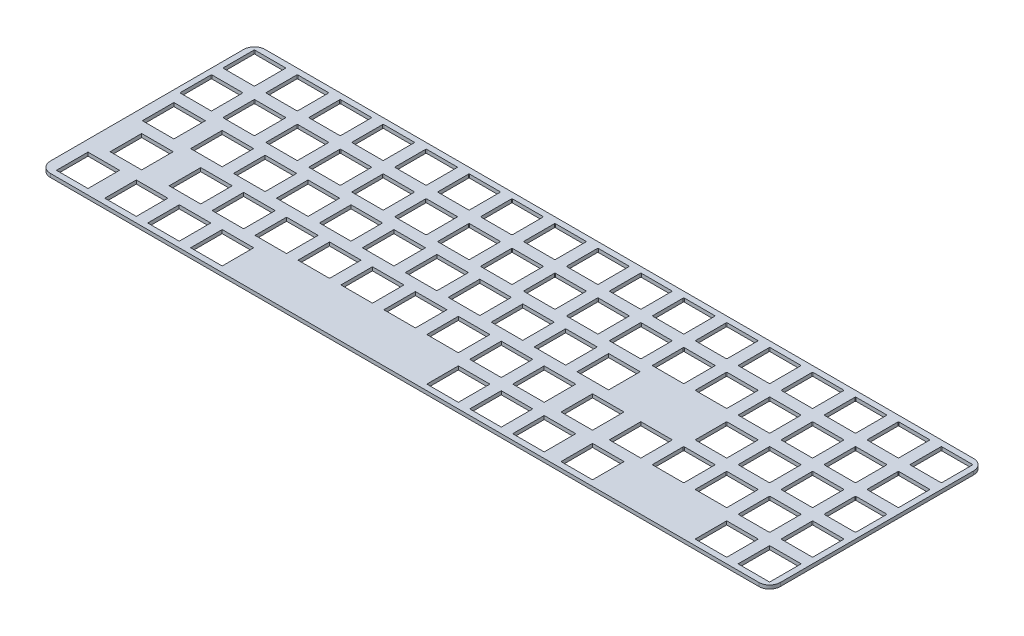
SolidWorks part; units mm, degrees
ref_plane "Front" through (0, 0, 0) normal (0, 0, 1) x (1, 0, 0)
ref_plane "Top" through (0, 0, 0) normal (0, 1, 0) x (1, 0, 0)
ref_plane "Right" through (0, 0, 0) normal (1, 0, 0) x (0, 0, -1)
sketch "Sketch1" plane through (0, 0, 0) normal (0, 1, 0) x (1, 0, 0)
  line L0 (-161.925, 28.575) -> (161.925, 28.575)
  line L1 (161.925, -47.625) -> (-161.925, -47.625)
  line L2 (161.925, -47.625) -> (161.925, 47.625)
  line L3 (161.925, 47.625) -> (-161.925, 47.625)
  line L4 (-161.925, -47.625) -> (-161.925, 47.625)
  line L5 (-123.825, 47.625) -> (-123.825, 28.575)
  line L6 (-104.775, 47.625) -> (-104.775, 28.575)
  line L7 (-142.875, 47.625) -> (-142.875, 28.575)
  line L8 (-85.725, 47.625) -> (-85.725, 28.575)
  line L9 (-66.675, 47.625) -> (-66.675, 28.575)
  line L10 (-47.625, 47.625) -> (-47.625, 28.575)
  line L11 (-28.575, 47.625) -> (-28.575, 28.575)
  line L12 (-9.525, 47.625) -> (-9.525, 28.575)
  line L13 (9.525, 47.625) -> (9.525, 28.575)
  line L14 (28.575, 47.625) -> (28.575, 28.575)
  line L15 (47.625, 47.625) -> (47.625, 28.575)
  line L16 (66.675, 47.625) -> (66.675, 28.575)
  line L17 (85.725, 47.625) -> (85.725, 28.575)
  line L18 (104.775, 47.625) -> (104.775, 28.575)
  line L19 (123.825, 47.625) -> (123.825, 28.575)
  line L20 (142.875, 47.625) -> (142.875, 28.575)
  line L21 (-142.875, 47.625) -> (-123.825, 47.625) construction
  line L22 (-161.925, 9.525) -> (161.925, 9.525)
  line L23 (-142.875, 28.575) -> (-142.875, 9.525)
  line L24 (-123.825, 28.575) -> (-123.825, 9.525)
  line L25 (-104.775, 28.575) -> (-104.775, 9.525)
  line L26 (-85.725, 28.575) -> (-85.725, 9.525)
  line L27 (-66.675, 28.575) -> (-66.675, 9.525)
  line L28 (-47.625, 28.575) -> (-47.625, 9.525)
  line L29 (-28.575, 28.575) -> (-28.575, 9.525)
  line L30 (-9.525, 28.575) -> (-9.525, 9.525)
  line L31 (9.525, 28.575) -> (9.525, 9.525)
  line L32 (28.575, 28.575) -> (28.575, 9.525)
  line L33 (47.625, 28.575) -> (47.625, 9.525)
  line L34 (66.675, 28.575) -> (66.675, 9.525)
  line L35 (85.725, 28.575) -> (85.725, 9.525)
  line L36 (104.775, 28.575) -> (104.775, 9.525)
  line L37 (123.825, 28.575) -> (123.825, 9.525)
  line L38 (142.875, 28.575) -> (142.875, 9.525)
  line L39 (-142.875, 28.575) -> (-123.825, 28.575) construction
  line L40 (-161.925, -9.525) -> (161.925, -9.525)
  line L41 (-161.925, -28.575) -> (161.925, -28.575)
  line L42 (-138.1125, 9.525) -> (-138.1125, -9.525)
  line L43 (-128.5875, -9.525) -> (-128.5875, -28.575)
  line L44 (-138.1125, -28.575) -> (-138.1125, -47.625)
  line L45 (-119.0625, 9.525) -> (-119.0625, -9.525)
  line L46 (-100.0125, 9.525) -> (-100.0125, -9.525)
  line L47 (-80.9625, 9.525) -> (-80.9625, -9.525)
  line L48 (-61.9125, 9.525) -> (-61.9125, -9.525)
  line L49 (-42.8625, 9.525) -> (-42.8625, -9.525)
  line L50 (-23.8125, 9.525) -> (-23.8125, -9.525)
  line L51 (-4.7625, 9.525) -> (-4.7625, -9.525)
  line L52 (14.2875, 9.525) -> (14.2875, -9.525)
  line L53 (33.3375, 9.525) -> (33.3375, -9.525)
  line L54 (-138.1125, 9.525) -> (-119.0625, 9.525) construction
  line L55 (52.3875, 9.525) -> (52.3875, -9.525)
  line L56 (85.725, 9.525) -> (85.725, -9.525)
  line L57 (-109.5375, -9.525) -> (-109.5375, -28.575)
  line L58 (-90.4875, -9.525) -> (-90.4875, -28.575)
  line L59 (-71.4375, -9.525) -> (-71.4375, -28.575)
  line L60 (-52.3875, -9.525) -> (-52.3875, -28.575)
  line L61 (-33.3375, -9.525) -> (-33.3375, -28.575)
  line L62 (-14.2875, -9.525) -> (-14.2875, -28.575)
  line L63 (4.7625, -9.525) -> (4.7625, -28.575)
  line L64 (23.8125, -9.525) -> (23.8125, -28.575)
  line L65 (42.8625, -9.525) -> (42.8625, -28.575)
  line L66 (-128.5875, -9.525) -> (-109.5375, -9.525) construction
  line L67 (66.675, -9.525) -> (66.675, -28.575)
  line L68 (85.725, -9.525) -> (85.725, -28.575)
  line L69 (-119.0625, -28.575) -> (-119.0625, -47.625)
  line L70 (-100.0125, -28.575) -> (-100.0125, -47.625)
  line L71 (-80.9625, -28.575) -> (-80.9625, -47.625)
  line L72 (-138.1125, -28.575) -> (-119.0625, -28.575) construction
  line L73 (-47.625, -28.575) -> (-47.625, -47.625)
  line L74 (4.7625, -28.575) -> (4.7625, -47.625)
  line L75 (23.8125, -28.575) -> (23.8125, -47.625)
  line L76 (42.8625, -28.575) -> (42.8625, -47.625)
  line L77 (61.9125, -28.575) -> (61.9125, -47.625)
  line L78 (85.725, -28.575) -> (85.725, -47.625)
  line L79 (104.775, 9.525) -> (104.775, -9.525)
  line L80 (104.775, -9.525) -> (104.775, -28.575)
  line L81 (123.825, 9.525) -> (123.825, -9.525)
  line L82 (123.825, -9.525) -> (123.825, -28.575)
  line L83 (123.825, -28.575) -> (123.825, -47.625)
  line L84 (142.875, 9.525) -> (142.875, -9.525)
  line L85 (142.875, -9.525) -> (142.875, -28.575)
  line L86 (142.875, -28.575) -> (142.875, -47.625)
  line L87 (-161.925, 47.625) -> (-142.875, 28.575) construction
  line L88 (-142.875, 28.575) -> (-161.925, 9.525) construction
  line L89 (-161.925, 9.525) -> (-138.1125, -9.525) construction
  line L90 (-138.1125, -9.525) -> (-119.0625, 9.525) construction
  line L91 (-119.0625, 9.525) -> (-100.0125, -9.525) construction
  line L92 (-100.0125, -9.525) -> (-80.9625, 9.525) construction
  line L93 (-80.9625, 9.525) -> (-61.9125, -9.525) construction
  line L94 (-61.9125, -9.525) -> (-42.8625, 9.525) construction
  line L95 (-42.8625, 9.525) -> (-23.8125, -9.525) construction
  line L96 (-23.8125, -9.525) -> (-4.7625, 9.525) construction
  line L97 (-4.7625, 9.525) -> (14.2875, -9.525) construction
  line L98 (14.2875, -9.525) -> (33.3375, 9.525) construction
  line L99 (33.3375, 9.525) -> (52.3875, -9.525) construction
  line L100 (52.3875, -9.525) -> (85.725, 9.525) construction
  line L101 (85.725, 9.525) -> (104.775, -9.525) construction
  line L102 (104.775, -9.525) -> (85.725, -28.575) construction
  line L103 (85.725, -47.625) -> (123.825, -28.575) construction
  line L104 (85.725, -28.575) -> (123.825, -47.625) construction
  line L105 (123.825, -28.575) -> (104.775, -9.525) construction
  line L106 (104.775, -9.525) -> (123.825, 9.525) construction
  line L107 (123.825, 9.525) -> (104.775, 28.575) construction
  line L108 (104.775, 28.575) -> (123.825, 47.625) construction
  line L109 (123.825, 47.625) -> (142.875, 28.575) construction
  line L110 (142.875, 28.575) -> (123.825, 9.525) construction
  line L111 (123.825, 9.525) -> (142.875, -9.525) construction
  line L112 (142.875, -9.525) -> (123.825, -28.575) construction
  line L113 (123.825, -28.575) -> (142.875, -47.625) construction
  line L114 (142.875, -47.625) -> (161.925, -28.575) construction
  line L115 (161.925, -28.575) -> (142.875, -9.525) construction
  line L116 (142.875, -9.525) -> (161.925, 9.525) construction
  line L117 (161.925, 9.525) -> (142.875, 28.575) construction
  line L118 (142.875, 28.575) -> (161.925, 47.625) construction
  line L119 (161.925, -47.625) -> (142.875, -28.575) construction
  line L120 (142.875, -28.575) -> (123.825, -47.625) construction
  line L121 (85.725, -47.625) -> (61.9125, -28.575) construction
  line L122 (61.9125, -28.575) -> (42.8625, -47.625) construction
  line L123 (42.8625, -47.625) -> (23.8125, -28.575) construction
  line L124 (23.8125, -28.575) -> (42.8625, -9.525) construction
  line L125 (42.8625, -9.525) -> (66.675, -28.575) construction
  line L126 (66.675, -28.575) -> (85.725, -9.525) construction
  line L127 (85.725, -9.525) -> (104.775, -28.575) construction
  line L128 (104.775, -28.575) -> (123.825, -9.525) construction
  line L129 (123.825, -9.525) -> (142.875, -28.575) construction
  line L130 (142.875, -28.575) -> (161.925, -9.525) construction
  line L131 (161.925, -9.525) -> (142.875, 9.525) construction
  line L132 (142.875, 9.525) -> (123.825, -9.525) construction
  line L133 (123.825, -9.525) -> (104.775, 9.525) construction
  line L134 (104.775, 9.525) -> (85.725, -9.525) construction
  line L135 (85.725, -9.525) -> (52.3875, 9.525) construction
  line L136 (52.3875, 9.525) -> (33.3375, -9.525) construction
  line L137 (33.3375, -9.525) -> (14.2875, 9.525) construction
  line L138 (14.2875, 9.525) -> (-4.7625, -9.525) construction
  line L139 (-4.7625, -9.525) -> (-23.8125, 9.525) construction
  line L140 (-23.8125, 9.525) -> (-42.8625, -9.525) construction
  line L141 (-42.8625, -9.525) -> (-61.9125, 9.525) construction
  line L142 (-61.9125, 9.525) -> (-80.9625, -9.525) construction
  line L143 (-80.9625, -9.525) -> (-100.0125, 9.525) construction
  line L144 (-100.0125, 9.525) -> (-119.0625, -9.525) construction
  line L145 (-119.0625, -9.525) -> (-138.1125, 9.525) construction
  line L146 (-138.1125, 9.525) -> (-161.925, -9.525) construction
  line L147 (-161.925, -9.525) -> (-128.5875, -28.575) construction
  line L148 (-128.5875, -28.575) -> (-109.5375, -9.525) construction
  line L149 (-109.5375, -9.525) -> (-90.4875, -28.575) construction
  line L150 (-90.4875, -28.575) -> (-71.4375, -9.525) construction
  line L151 (-71.4375, -9.525) -> (-52.3875, -28.575) construction
  line L152 (-52.3875, -28.575) -> (-33.3375, -9.525) construction
  line L153 (-33.3375, -9.525) -> (-14.2875, -28.575) construction
  line L154 (-14.2875, -28.575) -> (4.7625, -9.525) construction
  line L155 (4.7625, -9.525) -> (23.8125, -28.575) construction
  line L156 (23.8125, -28.575) -> (4.7625, -47.625) construction
  line L157 (4.7625, -47.625) -> (-47.625, -28.575) construction
  line L158 (-47.625, -28.575) -> (-80.9625, -47.625) construction
  line L159 (-80.9625, -47.625) -> (-100.0125, -28.575) construction
  line L160 (-100.0125, -28.575) -> (-119.0625, -47.625) construction
  line L161 (-119.0625, -47.625) -> (-138.1125, -28.575) construction
  line L162 (-138.1125, -28.575) -> (-161.925, -47.625) construction
  line L163 (-161.925, -28.575) -> (-138.1125, -47.625) construction
  line L164 (-138.1125, -47.625) -> (-119.0625, -28.575) construction
  line L165 (-119.0625, -28.575) -> (-100.0125, -47.625) construction
  line L166 (-100.0125, -47.625) -> (-80.9625, -28.575) construction
  line L167 (-80.9625, -28.575) -> (-47.625, -47.625) construction
  line L168 (-47.625, -47.625) -> (4.7625, -28.575) construction
  line L169 (4.7625, -28.575) -> (23.8125, -47.625) construction
  line L170 (23.8125, -47.625) -> (42.8625, -28.575) construction
  line L171 (42.8625, -28.575) -> (61.9125, -47.625) construction
  line L172 (61.9125, -47.625) -> (85.725, -28.575) construction
  line L173 (85.725, -28.575) -> (66.675, -9.525) construction
  line L174 (66.675, -9.525) -> (42.8625, -28.575) construction
  line L175 (42.8625, -28.575) -> (23.8125, -9.525) construction
  line L176 (23.8125, -9.525) -> (4.7625, -28.575) construction
  line L177 (4.7625, -28.575) -> (-14.2875, -9.525) construction
  line L178 (-14.2875, -9.525) -> (-33.3375, -28.575) construction
  line L179 (-33.3375, -28.575) -> (-52.3875, -9.525) construction
  line L180 (-52.3875, -9.525) -> (-71.4375, -28.575) construction
  line L181 (-71.4375, -28.575) -> (-90.4875, -9.525) construction
  line L182 (-90.4875, -9.525) -> (-109.5375, -28.575) construction
  line L183 (-109.5375, -28.575) -> (-128.5875, -9.525) construction
  line L184 (-128.5875, -9.525) -> (-161.925, -28.575) construction
  line L185 (161.925, 28.575) -> (142.875, 9.525) construction
  line L186 (142.875, 9.525) -> (123.825, 28.575) construction
  line L187 (123.825, 28.575) -> (104.775, 9.525) construction
  line L188 (104.775, 9.525) -> (85.725, 28.575) construction
  line L189 (85.725, 28.575) -> (66.675, 9.525) construction
  line L190 (66.675, 9.525) -> (47.625, 28.575) construction
  line L191 (47.625, 28.575) -> (28.575, 9.525) construction
  line L192 (28.575, 9.525) -> (9.525, 28.575) construction
  line L193 (9.525, 28.575) -> (-9.525, 9.525) construction
  line L194 (-9.525, 9.525) -> (-28.575, 28.575) construction
  line L195 (-28.575, 28.575) -> (-47.625, 9.525) construction
  line L196 (-47.625, 9.525) -> (-66.675, 28.575) construction
  line L197 (-66.675, 28.575) -> (-85.725, 9.525) construction
  line L198 (-85.725, 9.525) -> (-104.775, 28.575) construction
  line L199 (-104.775, 28.575) -> (-123.825, 9.525) construction
  line L200 (-123.825, 9.525) -> (-142.875, 28.575) construction
  line L201 (-161.925, 28.575) -> (-142.875, 9.525) construction
  line L202 (-142.875, 9.525) -> (-123.825, 28.575) construction
  line L203 (-123.825, 28.575) -> (-104.775, 9.525) construction
  line L204 (-104.775, 9.525) -> (-85.725, 28.575) construction
  line L205 (-85.725, 28.575) -> (-66.675, 9.525) construction
  line L206 (-66.675, 9.525) -> (-47.625, 28.575) construction
  line L207 (-47.625, 28.575) -> (-28.575, 9.525) construction
  line L208 (-28.575, 9.525) -> (-9.525, 28.575) construction
  line L209 (-9.525, 28.575) -> (9.525, 9.525) construction
  line L210 (9.525, 9.525) -> (28.575, 28.575) construction
  line L211 (28.575, 28.575) -> (47.625, 9.525) construction
  line L212 (47.625, 9.525) -> (66.675, 28.575) construction
  line L213 (66.675, 28.575) -> (85.725, 9.525) construction
  line L214 (85.725, 9.525) -> (104.775, 28.575) construction
  line L215 (161.925, 28.575) -> (142.875, 47.625) construction
  line L216 (142.875, 47.625) -> (123.825, 28.575) construction
  line L217 (123.825, 28.575) -> (104.775, 47.625) construction
  line L218 (104.775, 47.625) -> (85.725, 28.575) construction
  line L219 (85.725, 28.575) -> (66.675, 47.625) construction
  line L220 (66.675, 47.625) -> (47.625, 28.575) construction
  line L221 (47.625, 28.575) -> (28.575, 47.625) construction
  line L222 (28.575, 47.625) -> (9.525, 28.575) construction
  line L223 (9.525, 28.575) -> (-9.525, 47.625) construction
  line L224 (-9.525, 47.625) -> (-28.575, 28.575) construction
  line L225 (-28.575, 28.575) -> (-47.625, 47.625) construction
  line L226 (-47.625, 47.625) -> (-66.675, 28.575) construction
  line L227 (-66.675, 28.575) -> (-85.725, 47.625) construction
  line L228 (-85.725, 47.625) -> (-104.775, 28.575) construction
  line L229 (-104.775, 28.575) -> (-123.825, 47.625) construction
  line L230 (-123.825, 47.625) -> (-142.875, 28.575) construction
  line L231 (-161.925, 28.575) -> (-142.875, 47.625) construction
  line L232 (-142.875, 47.625) -> (-123.825, 28.575) construction
  line L233 (-123.825, 28.575) -> (-104.775, 47.625) construction
  line L234 (-104.775, 47.625) -> (-85.725, 28.575) construction
  line L235 (-85.725, 28.575) -> (-66.675, 47.625) construction
  line L236 (-66.675, 47.625) -> (-47.625, 28.575) construction
  line L237 (-47.625, 28.575) -> (-28.575, 47.625) construction
  line L238 (-28.575, 47.625) -> (-9.525, 28.575) construction
  line L239 (-9.525, 28.575) -> (9.525, 47.625) construction
  line L240 (9.525, 47.625) -> (28.575, 28.575) construction
  line L241 (28.575, 28.575) -> (47.625, 47.625) construction
  line L242 (47.625, 47.625) -> (66.675, 28.575) construction
  line L243 (66.675, 28.575) -> (85.725, 47.625) construction
  line L244 (85.725, 47.625) -> (104.775, 28.575) construction
  line L245 (160.147, 50.6095) -> (-160.147, 50.6095)
  line L246 (164.9095, 45.847) -> (164.9095, -45.847)
  line L247 (160.147, -50.6095) -> (-160.147, -50.6095)
  line L248 (-164.9095, 45.847) -> (-164.9095, -45.847)
  arc A0 (164.9095, 45.847) -> (160.147, 50.6095) centre (160.147, 45.847) ccw
  arc A1 (160.147, -50.6095) -> (164.9095, -45.847) centre (160.147, -45.847) ccw
  arc A2 (-164.9095, -45.847) -> (-160.147, -50.6095) centre (-160.147, -45.847) ccw
  arc A3 (-160.147, 50.6095) -> (-164.9095, 45.847) centre (-160.147, 45.847) ccw
  point P145 (0, 0)
  point P146 (104.775, -38.1)
  point P147 (-152.4, 38.1)
  point P148 (-152.4, 19.05)
  point P149 (-150.0188, 0)
  point P150 (-145.2562, -19.05)
  point P151 (-150.0188, -38.1)
  point P152 (-128.5875, -38.1)
  point P153 (-119.0625, -19.05)
  point P154 (-128.5875, 0)
  point P155 (-133.35, 19.05)
  point P156 (-133.35, 38.1)
  point P157 (-114.3, 38.1)
  point P158 (-114.3, 19.05)
  point P159 (-109.5375, 0)
  point P160 (-100.0125, -19.05)
  point P161 (-90.4875, -38.1)
  point P162 (-109.5375, -38.1)
  point P163 (-64.2938, -38.1)
  point P164 (-21.4312, -38.1)
  point P165 (14.2875, -38.1)
  point P166 (33.3375, -38.1)
  point P167 (52.3875, -38.1)
  point P168 (73.8188, -38.1)
  point P169 (133.35, -38.1)
  point P170 (152.4, -38.1)
  point P171 (152.4, -19.05)
  point P172 (133.35, -19.05)
  point P173 (114.3, -19.05)
  point P174 (95.25, -19.05)
  point P175 (76.2, -19.05)
  point P176 (54.7687, -19.05)
  point P177 (33.3375, -19.05)
  point P178 (14.2875, -19.05)
  point P179 (-4.7625, -19.05)
  point P180 (-23.8125, -19.05)
  point P181 (-42.8625, -19.05)
  point P182 (-61.9125, -19.05)
  point P183 (-80.9625, -19.05)
  point P184 (-90.4875, 0)
  point P185 (-71.4375, 0)
  point P186 (-52.3875, 0)
  point P187 (-33.3375, 0)
  point P188 (-14.2875, 0)
  point P189 (4.7625, 0)
  point P190 (23.8125, 0)
  point P191 (42.8625, 0)
  point P192 (69.0563, 0)
  point P193 (95.25, 0)
  point P194 (114.3, 0)
  point P195 (133.35, 0)
  point P196 (152.4, 0)
  point P197 (152.4, 19.05)
  point P198 (133.35, 19.05)
  point P199 (114.3, 19.05)
  point P200 (95.25, 19.05)
  point P201 (76.2, 19.05)
  point P202 (57.15, 19.05)
  point P203 (38.1, 19.05)
  point P204 (19.05, 19.05)
  point P205 (0, 19.05)
  point P206 (-19.05, 19.05)
  point P207 (-38.1, 19.05)
  point P208 (-57.15, 19.05)
  point P209 (-76.2, 19.05)
  point P210 (-95.25, 19.05)
  point P211 (-95.25, 38.1)
  point P212 (-76.2, 38.1)
  point P213 (-57.15, 38.1)
  point P214 (-38.1, 38.1)
  point P215 (-19.05, 38.1)
  point P216 (0, 38.1)
  point P217 (19.05, 38.1)
  point P218 (38.1, 38.1)
  point P219 (57.15, 38.1)
  point P220 (76.2, 38.1)
  point P221 (95.25, 38.1)
  point P222 (114.3, 38.1)
  point P223 (133.35, 38.1)
  point P224 (152.4, 38.1)
  point P225 (-152.4, 38.1)
  point P226 (0, 0)
sketch "Sketch2" plane through (0, 0, 0) normal (0, 1, 0) x (1, 0, 0)
  line L0 (-161.925, 28.575) -> (-142.875, 47.625) construction
  line L1 (-145.7071, 45.0977) -> (-159.0929, 45.0977)
  line L2 (-145.4023, 44.7929) -> (-145.4023, 31.4071)
  line L3 (-145.7071, 31.1023) -> (-159.0929, 31.1023)
  line L4 (-159.3977, 44.7929) -> (-159.3977, 31.4071)
  line L5 (-152.4, 31.1023) -> (-152.4, 45.0977) construction
  line L6 (-145.4023, 38.1) -> (-159.3977, 38.1) construction
  line L7 (-126.3523, 38.1) -> (-140.3477, 38.1) construction
  line L8 (-133.35, 31.1023) -> (-133.35, 45.0977) construction
  line L9 (-126.6571, 45.0977) -> (-140.0429, 45.0977)
  line L10 (-126.3523, 44.7929) -> (-126.3523, 31.4071)
  line L11 (-140.3477, 44.7929) -> (-140.3477, 31.4071)
  line L12 (-126.6571, 31.1023) -> (-140.0429, 31.1023)
  line L13 (-107.3023, 38.1) -> (-121.2977, 38.1) construction
  line L14 (-114.3, 31.1023) -> (-114.3, 45.0977) construction
  line L15 (-107.6071, 45.0977) -> (-120.9929, 45.0977)
  line L16 (-107.3023, 44.7929) -> (-107.3023, 31.4071)
  line L17 (-121.2977, 44.7929) -> (-121.2977, 31.4071)
  line L18 (-107.6071, 31.1023) -> (-120.9929, 31.1023)
  line L19 (-88.2523, 38.1) -> (-102.2477, 38.1) construction
  line L20 (-95.25, 31.1023) -> (-95.25, 45.0977) construction
  line L21 (-88.5571, 45.0977) -> (-101.9429, 45.0977)
  line L22 (-88.2523, 44.7929) -> (-88.2523, 31.4071)
  line L23 (-102.2477, 44.7929) -> (-102.2477, 31.4071)
  line L24 (-88.5571, 31.1023) -> (-101.9429, 31.1023)
  line L25 (-69.2023, 38.1) -> (-83.1977, 38.1) construction
  line L26 (-76.2, 31.1023) -> (-76.2, 45.0977) construction
  line L27 (-69.5071, 45.0977) -> (-82.8929, 45.0977)
  line L28 (-69.2023, 44.7929) -> (-69.2023, 31.4071)
  line L29 (-83.1977, 44.7929) -> (-83.1977, 31.4071)
  line L30 (-69.5071, 31.1023) -> (-82.8929, 31.1023)
  line L31 (-50.1523, 38.1) -> (-64.1477, 38.1) construction
  line L32 (-57.15, 31.1023) -> (-57.15, 45.0977) construction
  line L33 (-50.4571, 45.0977) -> (-63.8429, 45.0977)
  line L34 (-50.1523, 44.7929) -> (-50.1523, 31.4071)
  line L35 (-64.1477, 44.7929) -> (-64.1477, 31.4071)
  line L36 (-50.4571, 31.1023) -> (-63.8429, 31.1023)
  line L37 (-31.1023, 38.1) -> (-45.0977, 38.1) construction
  line L38 (-38.1, 31.1023) -> (-38.1, 45.0977) construction
  line L39 (-31.4071, 45.0977) -> (-44.7929, 45.0977)
  line L40 (-31.1023, 44.7929) -> (-31.1023, 31.4071)
  line L41 (-45.0977, 44.7929) -> (-45.0977, 31.4071)
  line L42 (-31.4071, 31.1023) -> (-44.7929, 31.1023)
  line L43 (-12.0523, 38.1) -> (-26.0477, 38.1) construction
  line L44 (-19.05, 31.1023) -> (-19.05, 45.0977) construction
  line L45 (-12.3571, 45.0977) -> (-25.7429, 45.0977)
  line L46 (-12.0523, 44.7929) -> (-12.0523, 31.4071)
  line L47 (-26.0477, 44.7929) -> (-26.0477, 31.4071)
  line L48 (-12.3571, 31.1023) -> (-25.7429, 31.1023)
  line L49 (6.9977, 38.1) -> (-6.9977, 38.1) construction
  line L50 (0, 31.1023) -> (0, 45.0977) construction
  line L51 (6.6929, 45.0977) -> (-6.6929, 45.0977)
  line L52 (6.9977, 44.7929) -> (6.9977, 31.4071)
  line L53 (-6.9977, 44.7929) -> (-6.9977, 31.4071)
  line L54 (6.6929, 31.1023) -> (-6.6929, 31.1023)
  line L55 (26.0477, 38.1) -> (12.0523, 38.1) construction
  line L56 (19.05, 31.1023) -> (19.05, 45.0977) construction
  line L57 (25.7429, 45.0977) -> (12.3571, 45.0977)
  line L58 (26.0477, 44.7929) -> (26.0477, 31.4071)
  line L59 (12.0523, 44.7929) -> (12.0523, 31.4071)
  line L60 (25.7429, 31.1023) -> (12.3571, 31.1023)
  line L61 (45.0977, 38.1) -> (31.1023, 38.1) construction
  line L62 (38.1, 31.1023) -> (38.1, 45.0977) construction
  line L63 (44.7929, 45.0977) -> (31.4071, 45.0977)
  line L64 (45.0977, 44.7929) -> (45.0977, 31.4071)
  line L65 (31.1023, 44.7929) -> (31.1023, 31.4071)
  line L66 (44.7929, 31.1023) -> (31.4071, 31.1023)
  line L67 (64.1477, 38.1) -> (50.1523, 38.1) construction
  line L68 (57.15, 31.1023) -> (57.15, 45.0977) construction
  line L69 (63.8429, 45.0977) -> (50.4571, 45.0977)
  line L70 (64.1477, 44.7929) -> (64.1477, 31.4071)
  line L71 (50.1523, 44.7929) -> (50.1523, 31.4071)
  line L72 (63.8429, 31.1023) -> (50.4571, 31.1023)
  line L73 (83.1977, 38.1) -> (69.2023, 38.1) construction
  line L74 (76.2, 31.1023) -> (76.2, 45.0977) construction
  line L75 (82.8929, 45.0977) -> (69.5071, 45.0977)
  line L76 (83.1977, 44.7929) -> (83.1977, 31.4071)
  line L77 (69.2023, 44.7929) -> (69.2023, 31.4071)
  line L78 (82.8929, 31.1023) -> (69.5071, 31.1023)
  line L79 (102.2477, 38.1) -> (88.2523, 38.1) construction
  line L80 (95.25, 31.1023) -> (95.25, 45.0977) construction
  line L81 (101.9429, 45.0977) -> (88.5571, 45.0977)
  line L82 (102.2477, 44.7929) -> (102.2477, 31.4071)
  line L83 (88.2523, 44.7929) -> (88.2523, 31.4071)
  line L84 (101.9429, 31.1023) -> (88.5571, 31.1023)
  line L85 (121.2977, 38.1) -> (107.3023, 38.1) construction
  line L86 (114.3, 31.1023) -> (114.3, 45.0977) construction
  line L87 (120.9929, 45.0977) -> (107.6071, 45.0977)
  line L88 (121.2977, 44.7929) -> (121.2977, 31.4071)
  line L89 (107.3023, 44.7929) -> (107.3023, 31.4071)
  line L90 (120.9929, 31.1023) -> (107.6071, 31.1023)
  line L91 (140.3477, 38.1) -> (126.3523, 38.1) construction
  line L92 (133.35, 31.1023) -> (133.35, 45.0977) construction
  line L93 (140.0429, 45.0977) -> (126.6571, 45.0977)
  line L94 (140.3477, 44.7929) -> (140.3477, 31.4071)
  line L95 (126.3523, 44.7929) -> (126.3523, 31.4071)
  line L96 (140.0429, 31.1023) -> (126.6571, 31.1023)
  line L97 (159.3977, 38.1) -> (145.4023, 38.1) construction
  line L98 (152.4, 31.1023) -> (152.4, 45.0977) construction
  line L99 (159.0929, 45.0977) -> (145.7071, 45.0977)
  line L100 (159.3977, 44.7929) -> (159.3977, 31.4071)
  line L101 (145.4023, 44.7929) -> (145.4023, 31.4071)
  line L102 (159.0929, 31.1023) -> (145.7071, 31.1023)
  line L103 (-126.3523, 19.05) -> (-140.3477, 19.05) construction
  line L104 (-133.35, 12.0523) -> (-133.35, 26.0477) construction
  line L105 (-126.6571, 26.0477) -> (-140.0429, 26.0477)
  line L106 (-126.3523, 25.7429) -> (-126.3523, 12.3571)
  line L107 (-140.3477, 25.7429) -> (-140.3477, 12.3571)
  line L108 (-126.6571, 12.0523) -> (-140.0429, 12.0523)
  line L109 (-107.3023, 19.05) -> (-121.2977, 19.05) construction
  line L110 (-114.3, 12.0523) -> (-114.3, 26.0477) construction
  line L111 (-107.6071, 26.0477) -> (-120.9929, 26.0477)
  line L112 (-107.3023, 25.7429) -> (-107.3023, 12.3571)
  line L113 (-121.2977, 25.7429) -> (-121.2977, 12.3571)
  line L114 (-107.6071, 12.0523) -> (-120.9929, 12.0523)
  line L115 (-88.2523, 19.05) -> (-102.2477, 19.05) construction
  line L116 (-95.25, 12.0523) -> (-95.25, 26.0477) construction
  line L117 (-88.5571, 26.0477) -> (-101.9429, 26.0477)
  line L118 (-88.2523, 25.7429) -> (-88.2523, 12.3571)
  line L119 (-102.2477, 25.7429) -> (-102.2477, 12.3571)
  line L120 (-88.5571, 12.0523) -> (-101.9429, 12.0523)
  line L121 (-69.2023, 19.05) -> (-83.1977, 19.05) construction
  line L122 (-76.2, 12.0523) -> (-76.2, 26.0477) construction
  line L123 (-69.5071, 26.0477) -> (-82.8929, 26.0477)
  line L124 (-69.2023, 25.7429) -> (-69.2023, 12.3571)
  line L125 (-83.1977, 25.7429) -> (-83.1977, 12.3571)
  line L126 (-69.5071, 12.0523) -> (-82.8929, 12.0523)
  line L127 (-50.1523, 19.05) -> (-64.1477, 19.05) construction
  line L128 (-57.15, 12.0523) -> (-57.15, 26.0477) construction
  line L129 (-50.4571, 26.0477) -> (-63.8429, 26.0477)
  line L130 (-50.1523, 25.7429) -> (-50.1523, 12.3571)
  line L131 (-64.1477, 25.7429) -> (-64.1477, 12.3571)
  line L132 (-50.4571, 12.0523) -> (-63.8429, 12.0523)
  line L133 (-31.1023, 19.05) -> (-45.0977, 19.05) construction
  line L134 (-38.1, 12.0523) -> (-38.1, 26.0477) construction
  line L135 (-31.4071, 26.0477) -> (-44.7929, 26.0477)
  line L136 (-31.1023, 25.7429) -> (-31.1023, 12.3571)
  line L137 (-45.0977, 25.7429) -> (-45.0977, 12.3571)
  line L138 (-31.4071, 12.0523) -> (-44.7929, 12.0523)
  line L139 (-12.0523, 19.05) -> (-26.0477, 19.05) construction
  line L140 (-19.05, 12.0523) -> (-19.05, 26.0477) construction
  line L141 (-12.3571, 26.0477) -> (-25.7429, 26.0477)
  line L142 (-12.0523, 25.7429) -> (-12.0523, 12.3571)
  line L143 (-26.0477, 25.7429) -> (-26.0477, 12.3571)
  line L144 (-12.3571, 12.0523) -> (-25.7429, 12.0523)
  line L145 (6.9977, 19.05) -> (-6.9977, 19.05) construction
  line L146 (0, 12.0523) -> (0, 26.0477) construction
  line L147 (6.6929, 26.0477) -> (-6.6929, 26.0477)
  line L148 (6.9977, 25.7429) -> (6.9977, 12.3571)
  line L149 (-6.9977, 25.7429) -> (-6.9977, 12.3571)
  line L150 (6.6929, 12.0523) -> (-6.6929, 12.0523)
  line L151 (26.0477, 19.05) -> (12.0523, 19.05) construction
  line L152 (19.05, 12.0523) -> (19.05, 26.0477) construction
  line L153 (25.7429, 26.0477) -> (12.3571, 26.0477)
  line L154 (26.0477, 25.7429) -> (26.0477, 12.3571)
  line L155 (12.0523, 25.7429) -> (12.0523, 12.3571)
  line L156 (25.7429, 12.0523) -> (12.3571, 12.0523)
  line L157 (45.0977, 19.05) -> (31.1023, 19.05) construction
  line L158 (38.1, 12.0523) -> (38.1, 26.0477) construction
  line L159 (44.7929, 26.0477) -> (31.4071, 26.0477)
  line L160 (45.0977, 25.7429) -> (45.0977, 12.3571)
  line L161 (31.1023, 25.7429) -> (31.1023, 12.3571)
  line L162 (44.7929, 12.0523) -> (31.4071, 12.0523)
  line L163 (64.1477, 19.05) -> (50.1523, 19.05) construction
  line L164 (57.15, 12.0523) -> (57.15, 26.0477) construction
  line L165 (63.8429, 26.0477) -> (50.4571, 26.0477)
  line L166 (64.1477, 25.7429) -> (64.1477, 12.3571)
  line L167 (50.1523, 25.7429) -> (50.1523, 12.3571)
  line L168 (63.8429, 12.0523) -> (50.4571, 12.0523)
  line L169 (83.1977, 19.05) -> (69.2023, 19.05) construction
  line L170 (76.2, 12.0523) -> (76.2, 26.0477) construction
  line L171 (82.8929, 26.0477) -> (69.5071, 26.0477)
  line L172 (83.1977, 25.7429) -> (83.1977, 12.3571)
  line L173 (69.2023, 25.7429) -> (69.2023, 12.3571)
  line L174 (82.8929, 12.0523) -> (69.5071, 12.0523)
  line L175 (102.2477, 19.05) -> (88.2523, 19.05) construction
  line L176 (95.25, 12.0523) -> (95.25, 26.0477) construction
  line L177 (101.9429, 26.0477) -> (88.5571, 26.0477)
  line L178 (102.2477, 25.7429) -> (102.2477, 12.3571)
  line L179 (88.2523, 25.7429) -> (88.2523, 12.3571)
  line L180 (101.9429, 12.0523) -> (88.5571, 12.0523)
  line L181 (121.2977, 19.05) -> (107.3023, 19.05) construction
  line L182 (114.3, 12.0523) -> (114.3, 26.0477) construction
  line L183 (120.9929, 26.0477) -> (107.6071, 26.0477)
  line L184 (121.2977, 25.7429) -> (121.2977, 12.3571)
  line L185 (107.3023, 25.7429) -> (107.3023, 12.3571)
  line L186 (120.9929, 12.0523) -> (107.6071, 12.0523)
  line L187 (140.3477, 19.05) -> (126.3523, 19.05) construction
  line L188 (133.35, 12.0523) -> (133.35, 26.0477) construction
  line L189 (140.0429, 26.0477) -> (126.6571, 26.0477)
  line L190 (140.3477, 25.7429) -> (140.3477, 12.3571)
  line L191 (126.3523, 25.7429) -> (126.3523, 12.3571)
  line L192 (140.0429, 12.0523) -> (126.6571, 12.0523)
  line L193 (159.3977, 19.05) -> (145.4023, 19.05) construction
  line L194 (152.4, 12.0523) -> (152.4, 26.0477) construction
  line L195 (159.0929, 26.0477) -> (145.7071, 26.0477)
  line L196 (159.3977, 25.7429) -> (159.3977, 12.3571)
  line L197 (145.4023, 25.7429) -> (145.4023, 12.3571)
  line L198 (159.0929, 12.0523) -> (145.7071, 12.0523)
  line L199 (-145.4023, 19.05) -> (-159.3977, 19.05) construction
  line L200 (-152.4, 12.0523) -> (-152.4, 26.0477) construction
  line L201 (-145.7071, 26.0477) -> (-159.0929, 26.0477)
  line L202 (-145.4023, 25.7429) -> (-145.4023, 12.3571)
  line L203 (-159.3977, 25.7429) -> (-159.3977, 12.3571)
  line L204 (-145.7071, 12.0523) -> (-159.0929, 12.0523)
  line L205 (-100.0125, -26.0477) -> (-100.0125, -12.0523) construction
  line L210 (-138.1125, 9.525) -> (-161.925, -9.525) construction
  line L211 (-157.0164, -6.9977) -> (-143.021, -6.9977)
  line L212 (-157.0164, -6.9977) -> (-157.0164, 6.9977)
  line L213 (-138.2585, -12.0523) -> (-152.254, -12.0523)
  line L214 (-138.2585, -12.0523) -> (-138.2585, -26.0477)
  line L215 (-138.2585, -26.0477) -> (-152.254, -26.0477)
  line L216 (-152.254, -12.0523) -> (-152.254, -26.0477)
  line L217 (-145.2562, -26.0477) -> (-145.2562, -12.0523) construction
  line L218 (-138.2586, -19.05) -> (-152.254, -19.05) construction
  line L219 (-157.0164, 6.9977) -> (-143.021, 6.9977)
  line L220 (-143.021, -6.9977) -> (-143.021, 6.9977)
  line L221 (-150.0187, 6.9977) -> (-150.0187, -6.9977) construction
  line L222 (-157.0164, 0) -> (-143.021, 0) construction
  line L223 (-138.1125, -28.575) -> (-161.925, -47.625) construction
  line L224 (-143.021, -31.1023) -> (-157.0164, -31.1023)
  line L225 (-143.021, -31.1023) -> (-143.021, -45.0977)
  line L226 (-143.021, -45.0977) -> (-157.0164, -45.0977)
  line L227 (-157.0164, -31.1023) -> (-157.0164, -45.0977)
  line L228 (-150.0187, -45.0977) -> (-150.0187, -31.1023) construction
  line L229 (-143.021, -38.1) -> (-157.0164, -38.1) construction
  line L230 (-128.5875, -28.575) -> (-109.5375, -9.525) construction
  line L231 (-121.5898, 6.9977) -> (-135.5852, 6.9977)
  line L232 (-121.5898, 6.9977) -> (-121.5898, -6.9977)
  line L233 (-121.5898, -6.9977) -> (-135.5852, -6.9977)
  line L234 (-135.5852, 6.9977) -> (-135.5852, -6.9977)
  line L235 (-128.5875, -6.9977) -> (-128.5875, 6.9977) construction
  line L236 (-121.5898, 0) -> (-135.5852, 0) construction
  line L237 (-112.0648, -12.0523) -> (-126.0602, -12.0523)
  line L238 (-112.0648, -12.0523) -> (-112.0648, -26.0477)
  line L239 (-112.0648, -26.0477) -> (-126.0602, -26.0477)
  line L240 (-126.0602, -12.0523) -> (-126.0602, -26.0477)
  line L241 (-119.0625, -26.0477) -> (-119.0625, -12.0523) construction
  line L242 (-112.0648, -19.05) -> (-126.0602, -19.05) construction
  line L243 (-138.1125, -47.625) -> (-119.0625, -28.575) construction
  line L244 (-135.5852, -45.0977) -> (-121.5898, -45.0977)
  line L245 (-135.5852, -45.0977) -> (-135.5852, -31.1023)
  line L246 (-135.5852, -31.1023) -> (-121.5898, -31.1023)
  line L247 (-121.5898, -45.0977) -> (-121.5898, -31.1023)
  line L248 (-128.5875, -31.1023) -> (-128.5875, -45.0977) construction
  line L249 (-135.5852, -38.1) -> (-121.5898, -38.1) construction
  line L250 (-102.5398, -6.9977) -> (-116.5352, -6.9977)
  line L251 (-102.5398, 6.9977) -> (-102.5398, -6.9977)
  line L252 (-102.5398, 6.9977) -> (-116.5352, 6.9977)
  line L253 (-116.5352, 6.9977) -> (-116.5352, -6.9977)
  line L254 (-102.5398, 0) -> (-116.5352, 0) construction
  line L255 (-109.5375, -6.9977) -> (-109.5375, 6.9977) construction
  line L256 (-83.4898, -6.9977) -> (-97.4852, -6.9977)
  line L257 (-83.4898, 6.9977) -> (-83.4898, -6.9977)
  line L258 (-83.4898, 6.9977) -> (-97.4852, 6.9977)
  line L259 (-97.4852, 6.9977) -> (-97.4852, -6.9977)
  line L260 (-83.4898, 0) -> (-97.4852, 0) construction
  line L261 (-90.4875, -6.9977) -> (-90.4875, 6.9977) construction
  line L262 (-64.4398, -6.9977) -> (-78.4352, -6.9977)
  line L263 (-64.4398, 6.9977) -> (-64.4398, -6.9977)
  line L264 (-64.4398, 6.9977) -> (-78.4352, 6.9977)
  line L265 (-78.4352, 6.9977) -> (-78.4352, -6.9977)
  line L266 (-64.4398, 0) -> (-78.4352, 0) construction
  line L267 (-71.4375, -6.9977) -> (-71.4375, 6.9977) construction
  line L268 (-45.3898, -6.9977) -> (-59.3852, -6.9977)
  line L269 (-45.3898, 6.9977) -> (-45.3898, -6.9977)
  line L270 (-45.3898, 6.9977) -> (-59.3852, 6.9977)
  line L271 (-59.3852, 6.9977) -> (-59.3852, -6.9977)
  line L272 (-45.3898, 0) -> (-59.3852, 0) construction
  line L273 (-52.3875, -6.9977) -> (-52.3875, 6.9977) construction
  line L274 (-26.3398, -6.9977) -> (-40.3352, -6.9977)
  line L275 (-26.3398, 6.9977) -> (-26.3398, -6.9977)
  line L276 (-26.3398, 6.9977) -> (-40.3352, 6.9977)
  line L277 (-40.3352, 6.9977) -> (-40.3352, -6.9977)
  line L278 (-26.3398, 0) -> (-40.3352, 0) construction
  line L279 (-33.3375, -6.9977) -> (-33.3375, 6.9977) construction
  line L280 (-7.2898, -6.9977) -> (-21.2852, -6.9977)
  line L281 (-7.2898, 6.9977) -> (-7.2898, -6.9977)
  line L282 (-7.2898, 6.9977) -> (-21.2852, 6.9977)
  line L283 (-21.2852, 6.9977) -> (-21.2852, -6.9977)
  line L284 (-7.2898, 0) -> (-21.2852, 0) construction
  line L285 (-14.2875, -6.9977) -> (-14.2875, 6.9977) construction
  line L286 (11.7602, -6.9977) -> (-2.2352, -6.9977)
  line L287 (11.7602, 6.9977) -> (11.7602, -6.9977)
  line L288 (11.7602, 6.9977) -> (-2.2352, 6.9977)
  line L289 (-2.2352, 6.9977) -> (-2.2352, -6.9977)
  line L290 (11.7602, 0) -> (-2.2352, 0) construction
  line L291 (4.7625, -6.9977) -> (4.7625, 6.9977) construction
  line L292 (30.8102, -6.9977) -> (16.8148, -6.9977)
  line L293 (30.8102, 6.9977) -> (30.8102, -6.9977)
  line L294 (30.8102, 6.9977) -> (16.8148, 6.9977)
  line L295 (16.8148, 6.9977) -> (16.8148, -6.9977)
  line L296 (30.8102, 0) -> (16.8148, 0) construction
  line L297 (23.8125, -6.9977) -> (23.8125, 6.9977) construction
  line L298 (49.8602, -6.9977) -> (35.8648, -6.9977)
  line L299 (49.8602, 6.9977) -> (49.8602, -6.9977)
  line L300 (49.8602, 6.9977) -> (35.8648, 6.9977)
  line L301 (35.8648, 6.9977) -> (35.8648, -6.9977)
  line L302 (49.8602, 0) -> (35.8648, 0) construction
  line L303 (42.8625, -6.9977) -> (42.8625, 6.9977) construction
  line L304 (-93.0148, -19.05) -> (-107.0102, -19.05) construction
  line L305 (-93.0148, -12.0523) -> (-107.0102, -12.0523)
  line L306 (-93.0148, -12.0523) -> (-93.0148, -26.0477)
  line L307 (-93.0148, -26.0477) -> (-107.0102, -26.0477)
  line L308 (-107.0102, -12.0523) -> (-107.0102, -26.0477)
  line L309 (-80.9625, -26.0477) -> (-80.9625, -12.0523) construction
  line L310 (-73.9648, -19.05) -> (-87.9602, -19.05) construction
  line L311 (-73.9648, -12.0523) -> (-87.9602, -12.0523)
  line L312 (-73.9648, -12.0523) -> (-73.9648, -26.0477)
  line L313 (-73.9648, -26.0477) -> (-87.9602, -26.0477)
  line L314 (-87.9602, -12.0523) -> (-87.9602, -26.0477)
  line L315 (-61.9125, -26.0477) -> (-61.9125, -12.0523) construction
  line L316 (-54.9148, -19.05) -> (-68.9102, -19.05) construction
  line L317 (-54.9148, -12.0523) -> (-68.9102, -12.0523)
  line L318 (-54.9148, -12.0523) -> (-54.9148, -26.0477)
  line L319 (-54.9148, -26.0477) -> (-68.9102, -26.0477)
  line L320 (-68.9102, -12.0523) -> (-68.9102, -26.0477)
  line L321 (-42.8625, -26.0477) -> (-42.8625, -12.0523) construction
  line L322 (-35.8648, -19.05) -> (-49.8602, -19.05) construction
  line L323 (-35.8648, -12.0523) -> (-49.8602, -12.0523)
  line L324 (-35.8648, -12.0523) -> (-35.8648, -26.0477)
  line L325 (-35.8648, -26.0477) -> (-49.8602, -26.0477)
  line L326 (-49.8602, -12.0523) -> (-49.8602, -26.0477)
  line L327 (-23.8125, -26.0477) -> (-23.8125, -12.0523) construction
  line L328 (-16.8148, -19.05) -> (-30.8102, -19.05) construction
  line L329 (-16.8148, -12.0523) -> (-30.8102, -12.0523)
  line L330 (-16.8148, -12.0523) -> (-16.8148, -26.0477)
  line L331 (-16.8148, -26.0477) -> (-30.8102, -26.0477)
  line L332 (-30.8102, -12.0523) -> (-30.8102, -26.0477)
  line L333 (-4.7625, -26.0477) -> (-4.7625, -12.0523) construction
  line L334 (2.2352, -19.05) -> (-11.7602, -19.05) construction
  line L335 (2.2352, -12.0523) -> (-11.7602, -12.0523)
  line L336 (2.2352, -12.0523) -> (2.2352, -26.0477)
  line L337 (2.2352, -26.0477) -> (-11.7602, -26.0477)
  line L338 (-11.7602, -12.0523) -> (-11.7602, -26.0477)
  line L339 (14.2875, -26.0477) -> (14.2875, -12.0523) construction
  line L340 (21.2852, -19.05) -> (7.2898, -19.05) construction
  line L341 (21.2852, -12.0523) -> (7.2898, -12.0523)
  line L342 (21.2852, -12.0523) -> (21.2852, -26.0477)
  line L343 (21.2852, -26.0477) -> (7.2898, -26.0477)
  line L344 (7.2898, -12.0523) -> (7.2898, -26.0477)
  line L345 (33.3375, -26.0477) -> (33.3375, -12.0523) construction
  line L346 (40.3352, -19.05) -> (26.3398, -19.05) construction
  line L347 (40.3352, -12.0523) -> (26.3398, -12.0523)
  line L348 (40.3352, -12.0523) -> (40.3352, -26.0477)
  line L349 (40.3352, -26.0477) -> (26.3398, -26.0477)
  line L350 (26.3398, -12.0523) -> (26.3398, -26.0477)
  line L353 (-100.0125, -28.575) -> (-119.0625, -47.625) construction
  line L354 (-116.5352, -45.0977) -> (-102.5398, -45.0977)
  line L358 (-116.5352, -45.0977) -> (-116.5352, -31.1023)
  line L359 (-116.5352, -31.1023) -> (-102.5398, -31.1023)
  line L362 (-102.5398, -45.0977) -> (-102.5398, -31.1023)
  line L364 (-109.5375, -31.1023) -> (-109.5375, -45.0977) construction
  line L371 (-116.5352, -38.1) -> (-102.5398, -38.1) construction
  line L373 (-100.0125, -47.625) -> (-80.9625, -28.575) construction
  line L376 (-97.4852, -45.0977) -> (-83.4898, -45.0977)
  line L378 (-97.4852, -45.0977) -> (-97.4852, -31.1023)
  line L381 (101.9429, -6.9977) -> (88.5571, -6.9977)
  line L382 (-97.4852, -31.1023) -> (-83.4898, -31.1023)
  line L383 (-83.4898, -45.0977) -> (-83.4898, -31.1023)
  line L384 (-90.4875, -31.1023) -> (-90.4875, -45.0977) construction
  line L385 (-97.4852, -38.1) -> (-83.4898, -38.1) construction
  line L386 (23.8125, -47.625) -> (42.8625, -28.575) construction
  line L387 (7.2898, -45.0977) -> (21.2852, -45.0977)
  line L388 (7.2898, -45.0977) -> (7.2898, -31.1023)
  line L389 (7.2898, -31.1023) -> (21.2852, -31.1023)
  line L390 (21.2852, -45.0977) -> (21.2852, -31.1023)
  line L391 (14.2875, -31.1023) -> (14.2875, -45.0977) construction
  line L392 (7.2898, -38.1) -> (21.2852, -38.1) construction
  line L393 (26.3398, -45.0977) -> (40.3352, -45.0977)
  line L394 (26.3398, -45.0977) -> (26.3398, -31.1023)
  line L395 (26.3398, -31.1023) -> (40.3352, -31.1023)
  line L396 (40.3352, -45.0977) -> (40.3352, -31.1023)
  line L397 (33.3375, -31.1023) -> (33.3375, -45.0977) construction
  line L398 (26.3398, -38.1) -> (40.3352, -38.1) construction
  line L399 (61.9125, -28.575) -> (42.8625, -47.625) construction
  line L400 (45.3898, -45.0977) -> (59.3852, -45.0977)
  line L401 (45.3898, -45.0977) -> (45.3898, -31.1023)
  line L402 (45.3898, -31.1023) -> (59.3852, -31.1023)
  line L403 (59.3852, -45.0977) -> (59.3852, -31.1023)
  line L404 (52.3875, -31.1023) -> (52.3875, -45.0977) construction
  line L405 (45.3898, -38.1) -> (59.3852, -38.1) construction
  line L406 (102.2477, 6.6929) -> (102.2477, -6.6929)
  line L407 (66.821, -45.0977) -> (80.8165, -45.0977)
  line L408 (66.821, -45.0977) -> (66.821, -31.1023)
  line L409 (66.821, -31.1023) -> (80.8165, -31.1023)
  line L410 (80.8165, -45.0977) -> (80.8165, -31.1023)
  line L411 (73.8188, -31.1023) -> (73.8188, -45.0977) construction
  line L412 (66.821, -38.1) -> (80.8165, -38.1) construction
  line L413 (101.9429, 6.9977) -> (88.5571, 6.9977)
  line L414 (88.2523, 6.6929) -> (88.2523, -6.6929)
  line L415 (95.25, -6.9977) -> (95.25, 6.9977) construction
  line L416 (102.2477, 0) -> (88.2523, 0) construction
  line L417 (120.9929, -6.9977) -> (107.6071, -6.9977)
  line L418 (114.3, -6.9977) -> (114.3, 6.9977) construction
  line L419 (121.2977, 0) -> (107.3023, 0) construction
  line L420 (120.9929, 6.9977) -> (107.6071, 6.9977)
  line L421 (107.3023, 6.6929) -> (107.3023, -6.6929)
  line L422 (121.2977, 6.6929) -> (121.2977, -6.6929)
  line L423 (140.0429, 6.9977) -> (126.6571, 6.9977)
  line L424 (126.3523, 6.6929) -> (126.3523, -6.6929)
  line L425 (133.35, -6.9977) -> (133.35, 6.9977) construction
  line L426 (140.3477, 0) -> (126.3523, 0) construction
  line L427 (140.3477, 6.6929) -> (140.3477, -6.6929)
  line L428 (140.0429, -6.9977) -> (126.6571, -6.9977)
  line L429 (159.3977, 6.6929) -> (159.3977, -6.6929)
  line L430 (159.0929, -6.9977) -> (145.7071, -6.9977)
  line L431 (152.4, -6.9977) -> (152.4, 6.9977) construction
  line L432 (145.4023, 6.6929) -> (145.4023, -6.6929)
  line L433 (159.3977, 0) -> (145.4023, 0) construction
  line L434 (159.0929, 6.9977) -> (145.7071, 6.9977)
  line L435 (101.9429, -26.0477) -> (88.5571, -26.0477)
  line L436 (102.2477, -12.3571) -> (102.2477, -25.7429)
  line L437 (101.9429, -12.0523) -> (88.5571, -12.0523)
  line L438 (88.2523, -12.3571) -> (88.2523, -25.7429)
  line L439 (95.25, -26.0477) -> (95.25, -12.0523) construction
  line L440 (102.2477, -19.05) -> (88.2523, -19.05) construction
  line L441 (120.9929, -26.0477) -> (107.6071, -26.0477)
  line L442 (114.3, -26.0477) -> (114.3, -12.0523) construction
  line L443 (121.2977, -19.05) -> (107.3023, -19.05) construction
  line L444 (120.9929, -12.0523) -> (107.6071, -12.0523)
  line L445 (107.3023, -12.3571) -> (107.3023, -25.7429)
  line L446 (121.2977, -12.3571) -> (121.2977, -25.7429)
  line L447 (140.0429, -12.0523) -> (126.6571, -12.0523)
  line L448 (126.3523, -12.3571) -> (126.3523, -25.7429)
  line L449 (133.35, -26.0477) -> (133.35, -12.0523) construction
  line L450 (140.3477, -19.05) -> (126.3523, -19.05) construction
  line L451 (140.3477, -12.3571) -> (140.3477, -25.7429)
  line L452 (140.0429, -26.0477) -> (126.6571, -26.0477)
  line L453 (159.3977, -12.3571) -> (159.3977, -25.7429)
  line L454 (159.0929, -26.0477) -> (145.7071, -26.0477)
  line L455 (152.4, -26.0477) -> (152.4, -12.0523) construction
  line L456 (145.4023, -12.3571) -> (145.4023, -25.7429)
  line L457 (159.3977, -19.05) -> (145.4023, -19.05) construction
  line L458 (159.0929, -12.0523) -> (145.7071, -12.0523)
  line L459 (85.725, -28.575) -> (66.675, -9.525) construction
  line L460 (145.4023, -45.0977) -> (159.3977, -45.0977)
  line L461 (145.4023, -45.0977) -> (145.4023, -31.1023)
  line L462 (145.4023, -31.1023) -> (159.3977, -31.1023)
  line L463 (159.3977, -45.0977) -> (159.3977, -31.1023)
  line L464 (152.4, -31.1023) -> (152.4, -45.0977) construction
  line L465 (145.4023, -38.1) -> (159.3977, -38.1) construction
  line L466 (126.3523, -45.0977) -> (140.3477, -45.0977)
  line L467 (126.3523, -45.0977) -> (126.3523, -31.1023)
  line L468 (126.3523, -31.1023) -> (140.3477, -31.1023)
  line L469 (140.3477, -45.0977) -> (140.3477, -31.1023)
  line L470 (133.35, -31.1023) -> (133.35, -45.0977) construction
  line L471 (126.3523, -38.1) -> (140.3477, -38.1) construction
  line L472 (69.2023, -26.0477) -> (83.1977, -26.0477)
  line L473 (69.2023, -26.0477) -> (69.2023, -12.0523)
  line L474 (69.2023, -12.0523) -> (83.1977, -12.0523)
  line L475 (83.1977, -26.0477) -> (83.1977, -12.0523)
  line L476 (76.2, -12.0523) -> (76.2, -26.0477) construction
  line L477 (69.2023, -19.05) -> (83.1977, -19.05) construction
  line L479 (47.771, -26.0477) -> (61.7665, -26.0477)
  line L480 (47.771, -26.0477) -> (47.771, -12.0523)
  line L481 (47.771, -12.0523) -> (61.7665, -12.0523)
  line L482 (61.7665, -26.0477) -> (61.7665, -12.0523)
  line L483 (54.7687, -12.0523) -> (54.7687, -26.0477) construction
  line L484 (47.771, -19.05) -> (61.7665, -19.05) construction
  line L490 (157.1625, -47.625) -> (-157.1625, -47.625)
  line L496 (161.925, -42.8625) -> (161.925, 42.8625)
  line L497 (157.1625, 47.625) -> (-157.1625, 47.625)
  line L503 (-161.925, -42.8625) -> (-161.925, 42.8625)
  line L504 (0, 47.625) -> (0, -47.625) construction
  line L510 (161.925, 0) -> (-161.925, 0) construction
  arc A0 (-145.4023, 31.4071) -> (-145.7071, 31.1023) centre (-145.7071, 31.4071) cw
  arc A1 (-145.7071, 45.0977) -> (-145.4023, 44.7929) centre (-145.7071, 44.7929) cw
  arc A2 (-159.0929, 45.0977) -> (-159.3977, 44.7929) centre (-159.0929, 44.7929) ccw
  arc A3 (-159.0929, 31.1023) -> (-159.3977, 31.4071) centre (-159.0929, 31.4071) cw
  arc A4 (-126.6571, 45.0977) -> (-126.3523, 44.7929) centre (-126.6571, 44.7929) cw
  arc A5 (-140.0429, 45.0977) -> (-140.3477, 44.7929) centre (-140.0429, 44.7929) ccw
  arc A6 (-140.0429, 31.1023) -> (-140.3477, 31.4071) centre (-140.0429, 31.4071) cw
  arc A7 (-126.3523, 31.4071) -> (-126.6571, 31.1023) centre (-126.6571, 31.4071) cw
  arc A8 (-107.6071, 45.0977) -> (-107.3023, 44.7929) centre (-107.6071, 44.7929) cw
  arc A9 (-120.9929, 45.0977) -> (-121.2977, 44.7929) centre (-120.9929, 44.7929) ccw
  arc A10 (-120.9929, 31.1023) -> (-121.2977, 31.4071) centre (-120.9929, 31.4071) cw
  arc A11 (-107.3023, 31.4071) -> (-107.6071, 31.1023) centre (-107.6071, 31.4071) cw
  arc A12 (-88.5571, 45.0977) -> (-88.2523, 44.7929) centre (-88.5571, 44.7929) cw
  arc A13 (-101.9429, 45.0977) -> (-102.2477, 44.7929) centre (-101.9429, 44.7929) ccw
  arc A14 (-101.9429, 31.1023) -> (-102.2477, 31.4071) centre (-101.9429, 31.4071) cw
  arc A15 (-88.2523, 31.4071) -> (-88.5571, 31.1023) centre (-88.5571, 31.4071) cw
  arc A16 (-69.5071, 45.0977) -> (-69.2023, 44.7929) centre (-69.5071, 44.7929) cw
  arc A17 (-82.8929, 45.0977) -> (-83.1977, 44.7929) centre (-82.8929, 44.7929) ccw
  arc A18 (-82.8929, 31.1023) -> (-83.1977, 31.4071) centre (-82.8929, 31.4071) cw
  arc A19 (-69.2023, 31.4071) -> (-69.5071, 31.1023) centre (-69.5071, 31.4071) cw
  arc A20 (-50.4571, 45.0977) -> (-50.1523, 44.7929) centre (-50.4571, 44.7929) cw
  arc A21 (-63.8429, 45.0977) -> (-64.1477, 44.7929) centre (-63.8429, 44.7929) ccw
  arc A22 (-63.8429, 31.1023) -> (-64.1477, 31.4071) centre (-63.8429, 31.4071) cw
  arc A23 (-50.1523, 31.4071) -> (-50.4571, 31.1023) centre (-50.4571, 31.4071) cw
  arc A24 (-31.4071, 45.0977) -> (-31.1023, 44.7929) centre (-31.4071, 44.7929) cw
  arc A25 (-44.7929, 45.0977) -> (-45.0977, 44.7929) centre (-44.7929, 44.7929) ccw
  arc A26 (-44.7929, 31.1023) -> (-45.0977, 31.4071) centre (-44.7929, 31.4071) cw
  arc A27 (-31.1023, 31.4071) -> (-31.4071, 31.1023) centre (-31.4071, 31.4071) cw
  arc A28 (-12.3571, 45.0977) -> (-12.0523, 44.7929) centre (-12.3571, 44.7929) cw
  arc A29 (-25.7429, 45.0977) -> (-26.0477, 44.7929) centre (-25.7429, 44.7929) ccw
  arc A30 (-25.7429, 31.1023) -> (-26.0477, 31.4071) centre (-25.7429, 31.4071) cw
  arc A31 (-12.0523, 31.4071) -> (-12.3571, 31.1023) centre (-12.3571, 31.4071) cw
  arc A32 (6.6929, 45.0977) -> (6.9977, 44.7929) centre (6.6929, 44.7929) cw
  arc A33 (-6.6929, 45.0977) -> (-6.9977, 44.7929) centre (-6.6929, 44.7929) ccw
  arc A34 (-6.6929, 31.1023) -> (-6.9977, 31.4071) centre (-6.6929, 31.4071) cw
  arc A35 (6.9977, 31.4071) -> (6.6929, 31.1023) centre (6.6929, 31.4071) cw
  arc A36 (25.7429, 45.0977) -> (26.0477, 44.7929) centre (25.7429, 44.7929) cw
  arc A37 (12.3571, 45.0977) -> (12.0523, 44.7929) centre (12.3571, 44.7929) ccw
  arc A38 (12.3571, 31.1023) -> (12.0523, 31.4071) centre (12.3571, 31.4071) cw
  arc A39 (26.0477, 31.4071) -> (25.7429, 31.1023) centre (25.7429, 31.4071) cw
  arc A40 (44.7929, 45.0977) -> (45.0977, 44.7929) centre (44.7929, 44.7929) cw
  arc A41 (31.4071, 45.0977) -> (31.1023, 44.7929) centre (31.4071, 44.7929) ccw
  arc A42 (31.4071, 31.1023) -> (31.1023, 31.4071) centre (31.4071, 31.4071) cw
  arc A43 (45.0977, 31.4071) -> (44.7929, 31.1023) centre (44.7929, 31.4071) cw
  arc A44 (63.8429, 45.0977) -> (64.1477, 44.7929) centre (63.8429, 44.7929) cw
  arc A45 (50.4571, 45.0977) -> (50.1523, 44.7929) centre (50.4571, 44.7929) ccw
  arc A46 (50.4571, 31.1023) -> (50.1523, 31.4071) centre (50.4571, 31.4071) cw
  arc A47 (64.1477, 31.4071) -> (63.8429, 31.1023) centre (63.8429, 31.4071) cw
  arc A48 (82.8929, 45.0977) -> (83.1977, 44.7929) centre (82.8929, 44.7929) cw
  arc A49 (69.5071, 45.0977) -> (69.2023, 44.7929) centre (69.5071, 44.7929) ccw
  arc A50 (69.5071, 31.1023) -> (69.2023, 31.4071) centre (69.5071, 31.4071) cw
  arc A51 (83.1977, 31.4071) -> (82.8929, 31.1023) centre (82.8929, 31.4071) cw
  arc A52 (101.9429, 45.0977) -> (102.2477, 44.7929) centre (101.9429, 44.7929) cw
  arc A53 (88.5571, 45.0977) -> (88.2523, 44.7929) centre (88.5571, 44.7929) ccw
  arc A54 (88.5571, 31.1023) -> (88.2523, 31.4071) centre (88.5571, 31.4071) cw
  arc A55 (102.2477, 31.4071) -> (101.9429, 31.1023) centre (101.9429, 31.4071) cw
  arc A56 (120.9929, 45.0977) -> (121.2977, 44.7929) centre (120.9929, 44.7929) cw
  arc A57 (107.6071, 45.0977) -> (107.3023, 44.7929) centre (107.6071, 44.7929) ccw
  arc A58 (107.6071, 31.1023) -> (107.3023, 31.4071) centre (107.6071, 31.4071) cw
  arc A59 (121.2977, 31.4071) -> (120.9929, 31.1023) centre (120.9929, 31.4071) cw
  arc A60 (140.0429, 45.0977) -> (140.3477, 44.7929) centre (140.0429, 44.7929) cw
  arc A61 (126.6571, 45.0977) -> (126.3523, 44.7929) centre (126.6571, 44.7929) ccw
  arc A62 (126.6571, 31.1023) -> (126.3523, 31.4071) centre (126.6571, 31.4071) cw
  arc A63 (140.3477, 31.4071) -> (140.0429, 31.1023) centre (140.0429, 31.4071) cw
  arc A64 (159.0929, 45.0977) -> (159.3977, 44.7929) centre (159.0929, 44.7929) cw
  arc A65 (145.7071, 45.0977) -> (145.4023, 44.7929) centre (145.7071, 44.7929) ccw
  arc A66 (145.7071, 31.1023) -> (145.4023, 31.4071) centre (145.7071, 31.4071) cw
  arc A67 (159.3977, 31.4071) -> (159.0929, 31.1023) centre (159.0929, 31.4071) cw
  arc A68 (-126.6571, 26.0477) -> (-126.3523, 25.7429) centre (-126.6571, 25.7429) cw
  arc A69 (-140.0429, 26.0477) -> (-140.3477, 25.7429) centre (-140.0429, 25.7429) ccw
  arc A70 (-140.0429, 12.0523) -> (-140.3477, 12.3571) centre (-140.0429, 12.3571) cw
  arc A71 (-126.3523, 12.3571) -> (-126.6571, 12.0523) centre (-126.6571, 12.3571) cw
  arc A72 (-107.6071, 26.0477) -> (-107.3023, 25.7429) centre (-107.6071, 25.7429) cw
  arc A73 (-120.9929, 26.0477) -> (-121.2977, 25.7429) centre (-120.9929, 25.7429) ccw
  arc A74 (-120.9929, 12.0523) -> (-121.2977, 12.3571) centre (-120.9929, 12.3571) cw
  arc A75 (-107.3023, 12.3571) -> (-107.6071, 12.0523) centre (-107.6071, 12.3571) cw
  arc A76 (-88.5571, 26.0477) -> (-88.2523, 25.7429) centre (-88.5571, 25.7429) cw
  arc A77 (-101.9429, 26.0477) -> (-102.2477, 25.7429) centre (-101.9429, 25.7429) ccw
  arc A78 (-101.9429, 12.0523) -> (-102.2477, 12.3571) centre (-101.9429, 12.3571) cw
  arc A79 (-88.2523, 12.3571) -> (-88.5571, 12.0523) centre (-88.5571, 12.3571) cw
  arc A80 (-69.5071, 26.0477) -> (-69.2023, 25.7429) centre (-69.5071, 25.7429) cw
  arc A81 (-82.8929, 26.0477) -> (-83.1977, 25.7429) centre (-82.8929, 25.7429) ccw
  arc A82 (-82.8929, 12.0523) -> (-83.1977, 12.3571) centre (-82.8929, 12.3571) cw
  arc A83 (-69.2023, 12.3571) -> (-69.5071, 12.0523) centre (-69.5071, 12.3571) cw
  arc A84 (-50.4571, 26.0477) -> (-50.1523, 25.7429) centre (-50.4571, 25.7429) cw
  arc A85 (-63.8429, 26.0477) -> (-64.1477, 25.7429) centre (-63.8429, 25.7429) ccw
  arc A86 (-63.8429, 12.0523) -> (-64.1477, 12.3571) centre (-63.8429, 12.3571) cw
  arc A87 (-50.1523, 12.3571) -> (-50.4571, 12.0523) centre (-50.4571, 12.3571) cw
  arc A88 (-31.4071, 26.0477) -> (-31.1023, 25.7429) centre (-31.4071, 25.7429) cw
  arc A89 (-44.7929, 26.0477) -> (-45.0977, 25.7429) centre (-44.7929, 25.7429) ccw
  arc A90 (-44.7929, 12.0523) -> (-45.0977, 12.3571) centre (-44.7929, 12.3571) cw
  arc A91 (-31.1023, 12.3571) -> (-31.4071, 12.0523) centre (-31.4071, 12.3571) cw
  arc A92 (-12.3571, 26.0477) -> (-12.0523, 25.7429) centre (-12.3571, 25.7429) cw
  arc A93 (-25.7429, 26.0477) -> (-26.0477, 25.7429) centre (-25.7429, 25.7429) ccw
  arc A94 (-25.7429, 12.0523) -> (-26.0477, 12.3571) centre (-25.7429, 12.3571) cw
  arc A95 (-12.0523, 12.3571) -> (-12.3571, 12.0523) centre (-12.3571, 12.3571) cw
  arc A96 (6.6929, 26.0477) -> (6.9977, 25.7429) centre (6.6929, 25.7429) cw
  arc A97 (-6.6929, 26.0477) -> (-6.9977, 25.7429) centre (-6.6929, 25.7429) ccw
  arc A98 (-6.6929, 12.0523) -> (-6.9977, 12.3571) centre (-6.6929, 12.3571) cw
  arc A99 (6.9977, 12.3571) -> (6.6929, 12.0523) centre (6.6929, 12.3571) cw
  arc A100 (25.7429, 26.0477) -> (26.0477, 25.7429) centre (25.7429, 25.7429) cw
  arc A101 (12.3571, 26.0477) -> (12.0523, 25.7429) centre (12.3571, 25.7429) ccw
  arc A102 (12.3571, 12.0523) -> (12.0523, 12.3571) centre (12.3571, 12.3571) cw
  arc A103 (26.0477, 12.3571) -> (25.7429, 12.0523) centre (25.7429, 12.3571) cw
  arc A104 (44.7929, 26.0477) -> (45.0977, 25.7429) centre (44.7929, 25.7429) cw
  arc A105 (31.4071, 26.0477) -> (31.1023, 25.7429) centre (31.4071, 25.7429) ccw
  arc A106 (31.4071, 12.0523) -> (31.1023, 12.3571) centre (31.4071, 12.3571) cw
  arc A107 (45.0977, 12.3571) -> (44.7929, 12.0523) centre (44.7929, 12.3571) cw
  arc A108 (63.8429, 26.0477) -> (64.1477, 25.7429) centre (63.8429, 25.7429) cw
  arc A109 (50.4571, 26.0477) -> (50.1523, 25.7429) centre (50.4571, 25.7429) ccw
  arc A110 (50.4571, 12.0523) -> (50.1523, 12.3571) centre (50.4571, 12.3571) cw
  arc A111 (64.1477, 12.3571) -> (63.8429, 12.0523) centre (63.8429, 12.3571) cw
  arc A112 (82.8929, 26.0477) -> (83.1977, 25.7429) centre (82.8929, 25.7429) cw
  arc A113 (69.5071, 26.0477) -> (69.2023, 25.7429) centre (69.5071, 25.7429) ccw
  arc A114 (69.5071, 12.0523) -> (69.2023, 12.3571) centre (69.5071, 12.3571) cw
  arc A115 (83.1977, 12.3571) -> (82.8929, 12.0523) centre (82.8929, 12.3571) cw
  arc A116 (101.9429, 26.0477) -> (102.2477, 25.7429) centre (101.9429, 25.7429) cw
  arc A117 (88.5571, 26.0477) -> (88.2523, 25.7429) centre (88.5571, 25.7429) ccw
  arc A118 (88.5571, 12.0523) -> (88.2523, 12.3571) centre (88.5571, 12.3571) cw
  arc A119 (102.2477, 12.3571) -> (101.9429, 12.0523) centre (101.9429, 12.3571) cw
  arc A120 (120.9929, 26.0477) -> (121.2977, 25.7429) centre (120.9929, 25.7429) cw
  arc A121 (107.6071, 26.0477) -> (107.3023, 25.7429) centre (107.6071, 25.7429) ccw
  arc A122 (107.6071, 12.0523) -> (107.3023, 12.3571) centre (107.6071, 12.3571) cw
  arc A123 (121.2977, 12.3571) -> (120.9929, 12.0523) centre (120.9929, 12.3571) cw
  arc A124 (140.0429, 26.0477) -> (140.3477, 25.7429) centre (140.0429, 25.7429) cw
  arc A125 (126.6571, 26.0477) -> (126.3523, 25.7429) centre (126.6571, 25.7429) ccw
  arc A126 (126.6571, 12.0523) -> (126.3523, 12.3571) centre (126.6571, 12.3571) cw
  arc A127 (140.3477, 12.3571) -> (140.0429, 12.0523) centre (140.0429, 12.3571) cw
  arc A128 (159.0929, 26.0477) -> (159.3977, 25.7429) centre (159.0929, 25.7429) cw
  arc A129 (145.7071, 26.0477) -> (145.4023, 25.7429) centre (145.7071, 25.7429) ccw
  arc A130 (145.7071, 12.0523) -> (145.4023, 12.3571) centre (145.7071, 12.3571) cw
  arc A131 (159.3977, 12.3571) -> (159.0929, 12.0523) centre (159.0929, 12.3571) cw
  arc A132 (-145.7071, 26.0477) -> (-145.4023, 25.7429) centre (-145.7071, 25.7429) cw
  arc A133 (-159.0929, 26.0477) -> (-159.3977, 25.7429) centre (-159.0929, 25.7429) ccw
  arc A134 (-159.0929, 12.0523) -> (-159.3977, 12.3571) centre (-159.0929, 12.3571) cw
  arc A135 (-145.4023, 12.3571) -> (-145.7071, 12.0523) centre (-145.7071, 12.3571) cw
  arc A136 (101.9429, 6.9977) -> (102.2477, 6.6929) centre (101.9429, 6.6929) cw
  arc A137 (107.6071, 6.9977) -> (107.3023, 6.6929) centre (107.6071, 6.6929) ccw
  arc A138 (107.6071, -6.9977) -> (107.3023, -6.6929) centre (107.6071, -6.6929) cw
  arc A139 (102.2477, -6.6929) -> (101.9429, -6.9977) centre (101.9429, -6.6929) cw
  arc A140 (88.5571, -6.9977) -> (88.2523, -6.6929) centre (88.5571, -6.6929) cw
  arc A141 (88.5571, 6.9977) -> (88.2523, 6.6929) centre (88.5571, 6.6929) ccw
  arc A142 (121.2977, -6.6929) -> (120.9929, -6.9977) centre (120.9929, -6.6929) cw
  arc A143 (120.9929, 6.9977) -> (121.2977, 6.6929) centre (120.9929, 6.6929) cw
  arc A144 (126.6571, 6.9977) -> (126.3523, 6.6929) centre (126.6571, 6.6929) ccw
  arc A145 (140.0429, 6.9977) -> (140.3477, 6.6929) centre (140.0429, 6.6929) cw
  arc A146 (140.3477, -6.6929) -> (140.0429, -6.9977) centre (140.0429, -6.6929) cw
  arc A147 (126.6571, -6.9977) -> (126.3523, -6.6929) centre (126.6571, -6.6929) cw
  arc A148 (159.3977, -6.6929) -> (159.0929, -6.9977) centre (159.0929, -6.6929) cw
  arc A149 (145.7071, -6.9977) -> (145.4023, -6.6929) centre (145.7071, -6.6929) cw
  arc A150 (159.0929, 6.9977) -> (159.3977, 6.6929) centre (159.0929, 6.6929) cw
  arc A151 (145.7071, 6.9977) -> (145.4023, 6.6929) centre (145.7071, 6.6929) ccw
  arc A152 (101.9429, -12.0523) -> (102.2477, -12.3571) centre (101.9429, -12.3571) cw
  arc A153 (107.6071, -12.0523) -> (107.3023, -12.3571) centre (107.6071, -12.3571) ccw
  arc A154 (107.6071, -26.0477) -> (107.3023, -25.7429) centre (107.6071, -25.7429) cw
  arc A155 (102.2477, -25.7429) -> (101.9429, -26.0477) centre (101.9429, -25.7429) cw
  arc A156 (88.5571, -26.0477) -> (88.2523, -25.7429) centre (88.5571, -25.7429) cw
  arc A157 (88.5571, -12.0523) -> (88.2523, -12.3571) centre (88.5571, -12.3571) ccw
  arc A158 (121.2977, -25.7429) -> (120.9929, -26.0477) centre (120.9929, -25.7429) cw
  arc A159 (120.9929, -12.0523) -> (121.2977, -12.3571) centre (120.9929, -12.3571) cw
  arc A160 (126.6571, -12.0523) -> (126.3523, -12.3571) centre (126.6571, -12.3571) ccw
  arc A161 (140.0429, -12.0523) -> (140.3477, -12.3571) centre (140.0429, -12.3571) cw
  arc A162 (140.3477, -25.7429) -> (140.0429, -26.0477) centre (140.0429, -25.7429) cw
  arc A163 (126.6571, -26.0477) -> (126.3523, -25.7429) centre (126.6571, -25.7429) cw
  arc A164 (159.3977, -25.7429) -> (159.0929, -26.0477) centre (159.0929, -25.7429) cw
  arc A165 (145.7071, -26.0477) -> (145.4023, -25.7429) centre (145.7071, -25.7429) cw
  arc A166 (159.0929, -12.0523) -> (159.3977, -12.3571) centre (159.0929, -12.3571) cw
  arc A167 (145.7071, -12.0523) -> (145.4023, -12.3571) centre (145.7071, -12.3571) ccw
  arc A168 (161.925, 42.8625) -> (157.1625, 47.625) centre (157.1625, 42.8625) ccw
  arc A169 (157.1625, -47.625) -> (161.925, -42.8625) centre (157.1625, -42.8625) ccw
  arc A170 (-157.1625, -47.625) -> (-161.925, -42.8625) centre (-157.1625, -42.8625) cw
  arc A171 (-157.1625, 47.625) -> (-161.925, 42.8625) centre (-157.1625, 42.8625) ccw
  point P0 (-152.4, 38.1)
  point P15 (-159.3977, 31.1023)
  point P16 (-150.0187, 0)
  point P552 (-109.5375, -38.1)
  point P558 (-145.2562, -19.05)
  point P562 (-150.0187, -38.1)
  point P568 (-128.5875, 0)
  point P572 (-119.0625, -19.05)
  point P578 (-128.5875, -38.1)
  point P759 (-90.4875, -38.1)
  point P765 (14.2875, -38.1)
  point P769 (33.3375, -38.1)
  point P775 (52.3875, -38.1)
  point P781 (73.8188, -38.1)
  point P786 (152.4, -38.1)
  point P950 (133.35, -38.1)
  point P954 (76.2, -19.05)
  point P960 (54.7687, -19.05)
  point P964 (0, 0)
  point P970 (161.925, 47.625)
  point P978 (-161.925, 47.625)
  dimension "D1" = 0.3048
  dimension "D10" = 4.7625
  dimension "D2" = 13.9954
  dimension "D8" = 323.85
  dimension "D9" = 95.25
  dimension "D3" = 17
  dimension "D4" = 2
  dimension "D5" = 10
  dimension "D6" = 9
  dimension "D7" = 3
extrude "Boss-Extrude1" add sketch "Sketch2" along normal mid plane 1.5875
